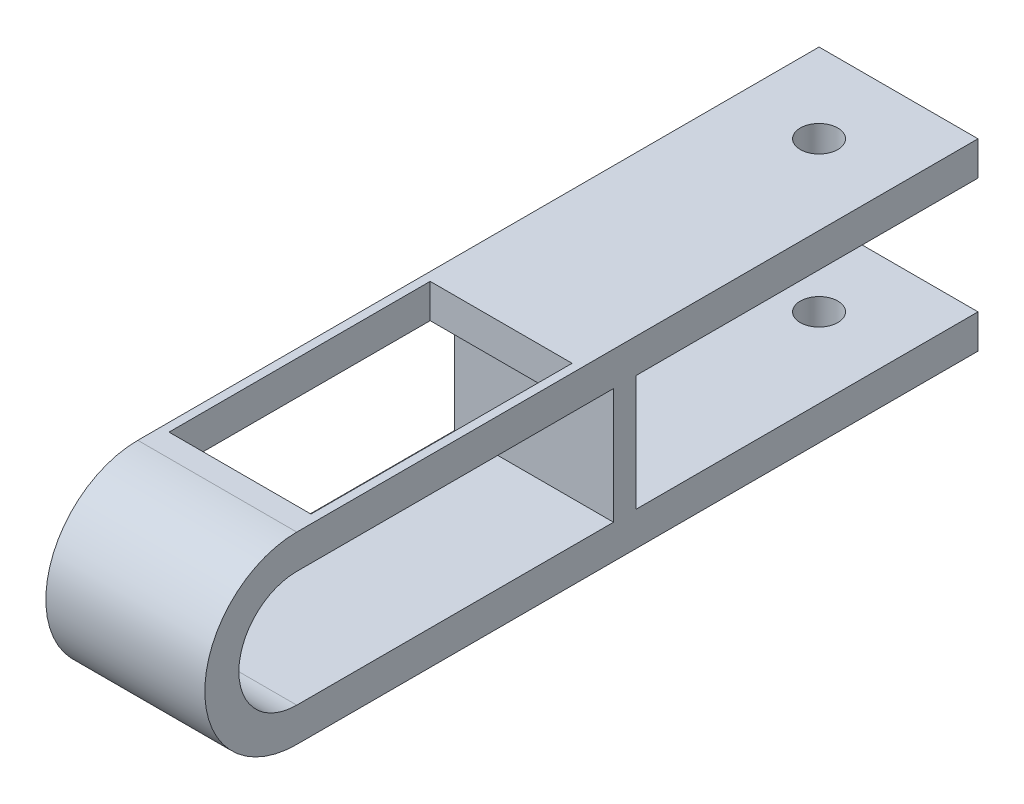
SolidWorks part; units mm, degrees
ref_plane "Front Plane" through (0, 0, 0) normal (1, 0, 0) x (0, 1, 0)
ref_plane "Top Plane" through (0, 0, 0) normal (0, 0, 1) x (0, 1, 0)
ref_plane "Right Plane" through (0, 0, 0) normal (0, 1, 0) x (-1, 0, 0)
sketch "Sketch2" plane through (0, 0, 0) normal (1, 0, 0) x (0, 1, 0)
  line L0 (0, 0) -> (0, 67.6733) construction
  line L1 (8.1, 0) -> (5.1, 0)
  line L3 (-8.1, 60) -> (-8.1, 0)
  line L4 (-8.1, 0) -> (-5.1, 0)
  line L5 (-5.1, 60) -> (-5.1, 32.1)
  line L6 (5.1, 60) -> (5.1, 32.1)
  line L8 (8.1, 60) -> (8.1, 0)
  line L9 (0, 0) -> (-21.6048, 0) construction
  line L10 (-5.1, 30.1) -> (-5.1, 0)
  line L11 (-5.1, 32.1) -> (5.1, 32.1)
  line L13 (-5.1, 30.1) -> (5.1, 30.1)
  line L15 (5.1, 30.1) -> (5.1, 0)
  arc A0 (5.1, 60) -> (-5.1, 60) centre (0, 60) ccw
  arc A1 (8.1, 60) -> (-8.1, 60) centre (0, 60) ccw
  point P16 (0, 65.1)
  dimension "D4" = 2
  dimension "D1" = 3
  dimension "D2" = 60
  dimension "D3" = 5.1
  dimension "D5" = 33
extrude "Boss-Extrude1" add sketch "Sketch2" along normal blind 14
sketch "Sketch3" plane through (0, -8.1, 0) normal (0, -1, 0) x (1, 0, 0)
  line L0 (7, 0) -> (7, 60) construction
  line L1 (14, 0) -> (0, 0) construction
  line L2 (14, 60) -> (0, 60) construction
  line L3 (0, 60) -> (0, 0) construction
  line L4 (14, 60) -> (14, 0) construction
  circle A0 centre (7, 7) radius 1.65
  dimension "D1" = 3.3
  dimension "D2" = 7
extrude "Cut-Extrude1" cut sketch "Sketch3" against normal blind 40
sketch "Sketch4" plane through (0, -8.1, 0) normal (0, -1, 0) x (1, 0, 0)
  line L0 (7, 60) -> (7, 40.4256) construction
  line L1 (14, 60) -> (0, 60) construction
  line L2 (9.35, 38) -> (10.6, 53)
  line L3 (3.4, 53) -> (4.65, 38)
  circle A0 centre (7, 53) radius 3.6
  circle A1 centre (7, 38) radius 2.35
  dimension "D1" = 7.2
  dimension "D2" = 4.7
  dimension "D3" = 7
  dimension "D4" = 15
extrude "Cut-Extrude2" cut sketch "Sketch4" against normal blind 1.5 contours A1 L2 A0 L3 | L0 A0 L3 | A0 L0 L2 | A1 region at (8.5274, -8.1, 53.0001) region at (5.4726, -8.1, 53.0001) region at (9.4291, -8.1, 50.1292) region at (7, -8.1, 38)
sketch "Sketch6" plane through (0, -6.6, 0) normal (0, -1, 0) x (1, 0, 0)
  line L0 (7, 35.65) -> (7, 56.6) construction
  circle A0 centre (7, 38) radius 0.15
  arc A1 (4.65, 38) -> (9.35, 38) centre (7, 38) ccw construction
  arc A2 (10.6, 53) -> (3.4, 53) centre (7, 53) ccw construction
  arc A3 (4.65, 38) -> (9.35, 38) centre (7, 38) ccw construction
  dimension "D1" = 0.3
extrude "Cut-Extrude3" cut sketch "Sketch6" against normal blind 0.5
ref_plane "Plane1" through (10.6, -8.1, 53) normal (0, 0, 1) x (1, 0, 0)
sketch "Sketch8" plane through (0, -6.6, 0) normal (0, -1, 0) x (1, 0, 0)
  circle A0 centre (7, 53) radius 0.15
  arc A1 (10.6, 53) -> (3.4, 53) centre (7, 53) ccw construction
  dimension "D1" = 0.3
extrude "Cut-Extrude4" cut sketch "Sketch8" against normal blind 0.5
sketch "Sketch9" plane through (0, 8.1, 0) normal (0, 1, 0) x (-1, 0, 0)
  line L1 (-14, 60) -> (0, 60) construction
  line L2 (-0.75, 35) -> (-13.25, 35)
  line L3 (-0.75, 35) -> (-0.75, 58)
  line L4 (-0.75, 58) -> (-13.25, 58)
  line L5 (-13.25, 35) -> (-13.25, 58)
  line L6 (-0.75, 35) -> (-13.25, 58) construction
  line L7 (-0.75, 58) -> (-13.25, 35) construction
  line L8 (-14, 0) -> (-14, 60) construction
  point P6 (-7, 46.5)
  dimension "D1" = 2
  dimension "D2" = 12.5
  dimension "23" = 23
  dimension "D3" = 0.75
extrude "Cut-Extrude5" cut sketch "Sketch9" against normal up to next
